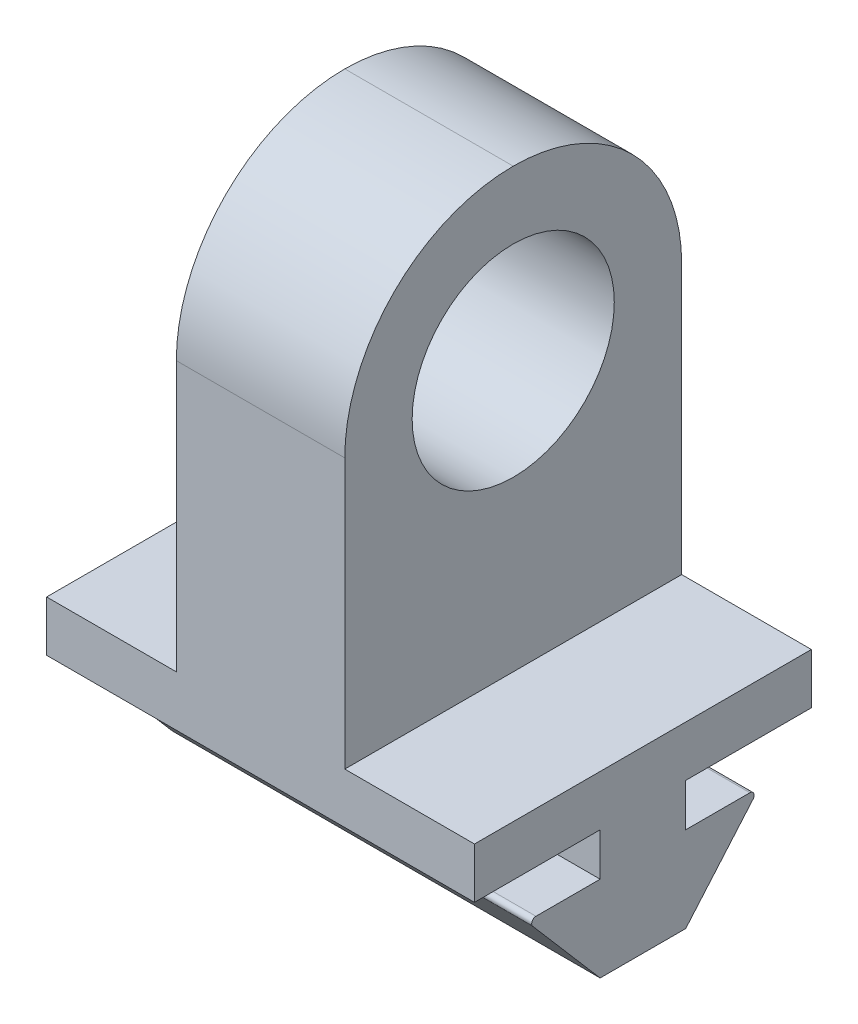
SolidWorks part; units mm, degrees
ref_plane "Front Plane" through (0, 0, 0) normal (0, 0, 1) x (1, 0, 0)
ref_plane "Top Plane" through (0, 0, 0) normal (0, 1, 0) x (1, 0, 0)
ref_plane "Right Plane" through (0, 0, 0) normal (1, 0, 0) x (0, 0, -1)
sketch "Sketch1" plane through (0, 0, 0) normal (0, 1, 0) x (1, 0, 0)
  line L1 (38.1, -25.4) -> (-38.1, -25.4)
  line L2 (38.1, -25.4) -> (38.1, 25.4)
  line L3 (38.1, 25.4) -> (-38.1, 25.4)
  line L4 (-38.1, -25.4) -> (-38.1, 25.4)
  line L5 (38.1, -25.4) -> (-38.1, 25.4) construction
  line L6 (38.1, 25.4) -> (-38.1, -25.4) construction
  point P0 (0, 0)
  dimension "D1" = 76.2
  dimension "D2" = 50.8
sketch "Sketch10" plane through (0, 0, 0) normal (1, 0, 0) x (0, 0, -1)
  line L0 (-12.7, 0) -> (0, 0) construction
  line L1 (0, 0) -> (0, -12.7) construction
  line L2 (0, 0) -> (0, 12.7) construction
  line L3 (0, 0) -> (12.7, 0) construction
  line L4 (6.35, 10.16) -> (-6.35, 10.16)
  line L5 (-6.5427, 9.7405) -> (-2.54, 5.08)
  line L6 (6.5427, 9.7405) -> (2.54, 5.08)
  line L7 (2.54, 5.08) -> (-2.54, 5.08)
  line L8 (-5.08, -2.54) -> (-5.08, 2.54)
  line L9 (-5.08, 2.54) -> (-9.7405, 6.5427)
  line L10 (-10.16, -6.35) -> (-10.16, 6.35)
  line L11 (-9.7405, -6.5427) -> (-5.08, -2.54)
  line L12 (-12.7, -2.54) -> (-12.7, 2.54)
  line L13 (-12.7, 2.54) -> (-10.16, 2.54)
  line L14 (-10.16, 2.54) -> (-10.16, -2.54)
  line L15 (-10.16, -2.54) -> (-12.7, -2.54)
  line L16 (2.54, 12.7) -> (-2.54, 12.7)
  line L17 (-2.54, 12.7) -> (-2.54, 10.16)
  line L18 (-2.54, 10.16) -> (2.54, 10.16)
  line L19 (2.54, 10.16) -> (2.54, 12.7)
  line L20 (2.54, -12.7) -> (-2.54, -12.7)
  line L21 (2.54, -5.08) -> (-2.54, -5.08)
  line L23 (6.35, -10.16) -> (-6.35, -10.16)
  line L24 (-2.54, -12.7) -> (-2.54, -10.16)
  line L26 (2.54, -12.7) -> (2.54, -10.16)
  line L27 (-2.54, -10.16) -> (2.54, -10.16)
  line L28 (-2.54, -5.08) -> (-6.5427, -9.7405)
  line L29 (2.54, -5.08) -> (6.5427, -9.7405)
  line L30 (5.08, -2.54) -> (5.08, 2.54)
  line L31 (12.7, -2.54) -> (12.7, 2.54)
  line L32 (12.7, 2.54) -> (10.16, 2.54)
  line L33 (10.16, 2.54) -> (10.16, -2.54)
  line L34 (10.16, -2.54) -> (12.7, -2.54)
  line L35 (10.16, -6.35) -> (10.16, 6.35)
  line L36 (5.08, 2.54) -> (9.7405, 6.5427)
  line L37 (5.08, -2.54) -> (9.7405, -6.5427)
  arc A0 (-10.16, -6.35) -> (-9.7405, -6.5427) centre (-9.906, -6.35) ccw
  arc A1 (-9.7405, 6.5427) -> (-10.16, 6.35) centre (-9.906, 6.35) ccw
  arc A2 (6.35, 10.16) -> (6.5427, 9.7405) centre (6.35, 9.906) cw
  arc A3 (-6.35, 10.16) -> (-6.5427, 9.7405) centre (-6.35, 9.906) ccw
  arc A4 (-6.35, -10.16) -> (-6.5427, -9.7405) centre (-6.35, -9.906) cw
  arc A6 (6.5427, -9.7405) -> (6.35, -10.16) centre (6.35, -9.906) cw
  arc A8 (9.7405, -6.5427) -> (10.16, -6.35) centre (9.906, -6.35) ccw
  arc A9 (10.16, 6.35) -> (9.7405, 6.5427) centre (9.906, 6.35) ccw
  point P4 (0, 5.08)
  point P10 (0, 10.16)
  point P17 (-5.08, 0)
  point P20 (-10.16, 0)
  point P30 (-12.7, 0)
  point P35 (0, 12.7)
  point P39 (0, -12.7)
  point P42 (0, -5.08)
  point P46 (0, -10.16)
  point P52 (5.08, 0)
  point P55 (12.7, 0)
  point P60 (10.16, 0)
  dimension "D1" = 0.254
  dimension "D16" = 0.254
  dimension "D2" = 5.08
  dimension "D3" = 5.08
  dimension "D4" = 2.54
  dimension "D5" = 2.54
  dimension "D6" = 5.08
  dimension "D7" = 12.7
  dimension "D8" = 5.08
  dimension "D9" = 12.7
  dimension "D10" = 5.08
  dimension "D11" = 5.08
  dimension "D12" = 12.7
  dimension "D13" = 5.08
  dimension "D14" = 5.08
  dimension "D15" = 2.54
extrude "Boss-Extrude3" add sketch "Sketch10" against normal blind 25.4 separate body contours L15 L10 L13 | L9 A1 L10 A0 L11 L8 | L4 A3 L5 L7 L6 A2 | L4 L19 L17 | A6 L29 L21 L28 A4 L23 | L20 L26 L23 L24 | L35 A9 L36 L30 L37 A8 L33 | L33 L34 L31 L32 region at (0, 8.0055, 0) region at (0, 11.43, 0) region at (0, 0, 8.0055) region at (0, 0, 11.43) region at (0, -11.43, 0) region at (0, -8.0055, 0) region at (0, 0, -8.0055) region at (0, 0, -11.43)
sketch "Sketch11" plane through (0, 0, 0) normal (1, 0, 0) x (0, 0, -1)
  line L0 (10, 12.7) -> (-10, 12.7)
  line L2 (-10, 12.7) -> (-10, 15.7)
  line L3 (-10, 15.7) -> (10, 15.7)
  line L4 (10, 15.7) -> (10, 12.7)
  line L5 (2.54, 12.7) -> (-2.54, 12.7) construction
  point P3 (0, 12.7)
  point P5 (0, 12.7)
  dimension "D1" = 3
  dimension "D2" = 20
extrude "Boss-Extrude4" add sketch "Sketch11" along direction (1, 0, 0) on the side against the normal up to surface (25.4 mm away) up to face at (-25.4, 9.5805, 0)
sketch "Sketch12" plane through (-25.4, 0, 0) normal (-1, 0, 0) x (0, 0, 1)
  line L0 (0, 0) -> (-15.4836, 16.021)
  line L1 (-15.4836, 16.021) -> (-15.4836, -14.9642)
  line L2 (-15.4836, -14.9642) -> (16.0161, -14.9642)
  line L3 (16.0161, -14.9642) -> (16.0161, 15.4789)
  line L4 (16.0161, 15.4789) -> (0, 0)
extrude "Cut-Extrude1" cut sketch "Sketch12" against normal through all
sketch "Sketch13" plane through (0, 0, -10) normal (0, 0, -1) x (-1, 0, 0)
  line L0 (12.7, 15.7) -> (12.7, 41.7) construction
  line L1 (25.4, 15.7) -> (0, 15.7) construction
  line L2 (17.7, 41.7) -> (7.7, 41.7)
  line L3 (7.7, 41.7) -> (7.7, 15.7)
  line L4 (7.7, 15.7) -> (17.7, 15.7)
  line L5 (17.7, 15.7) -> (17.7, 41.7)
  point P7 (12.7, 41.7)
  dimension "D1" = 26
  dimension "D2" = 10
extrude "Boss-Extrude5" add sketch "Sketch13" against normal through all
sketch "Sketch16" plane through (-17.7, 0, 0) normal (-1, 0, 0) x (0, 0, 1)
  line L0 (0, 31.7) -> (0, 15.7) construction
  line L1 (10, 15.7) -> (-10, 15.7) construction
  circle A0 centre (0, 31.7) radius 6
  dimension "D1" = 12
  dimension "D2" = 16
extrude "Cut-Extrude2" cut sketch "Sketch16" against normal through all
fillet "Fillet1" radius 10 2 edges at (-12.7, 41.7, 10) (-12.7, 41.7, -10)
